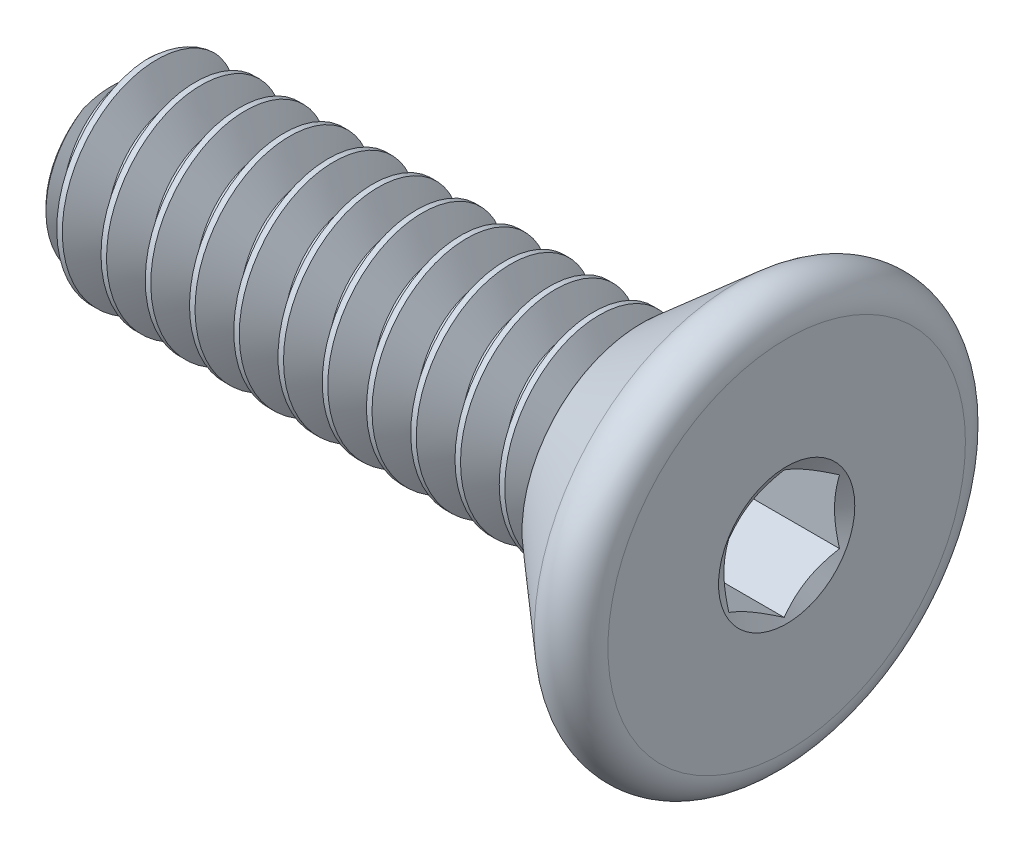
SolidWorks part; units mm, degrees
ref_plane "Front Plane" through (0, 0, 0) normal (0, 0, 1) x (1, 0, 0)
ref_plane "Top Plane" through (0, 0, 0) normal (0, 1, 0) x (1, 0, 0)
ref_plane "Right Plane" through (0, 0, 0) normal (1, 0, 0) x (0, 0, -1)
sketch "Sketch1" plane through (0, 0, 0) normal (0, 0, 1) x (1, 0, 0)
  line L0 (4.7625, 3.2385) -> (4.7625, -3.2385) construction
  line L1 (4.7625, 0) -> (-4.7625, 0) construction
  line L2 (-4.7625, 1.1049) -> (-4.7625, -1.1049) construction
  line L3 (-4.7625, 1.1049) -> (-4.445, 1.4224) construction
  line L4 (-4.445, 1.4224) -> (2.6543, 1.4224) construction
  line L8 (2.6543, 1.6941) -> (2.6543, -1.6941) construction
  line L9 (-4.7625, -1.1049) -> (-4.445, -1.4224) construction
  line L10 (-4.445, -1.4224) -> (2.6543, -1.4224) construction
  line L11 (2.6543, 1.6941) -> (4.037, 2.8961) construction
  line L12 (2.6543, -1.6941) -> (4.037, -2.8961) construction
  line L13 (4.3244, 2.7686) -> (4.3244, -2.7686) construction
  line L14 (2.6543, 1.6437) -> (2.7649, 1.6437) construction
  line L15 (2.7649, 1.6437) -> (2.7649, 1.533) construction
  line L16 (4.7625, 0.7937) -> (3.3655, 0.7937) construction
  line L17 (3.3655, 0.7937) -> (3.3655, -0.7938) construction
  line L18 (3.3655, -0.7938) -> (4.7625, -0.7938) construction
  line L19 (4.3244, -2.7686) -> (4.3244, -3.2385) construction
  line L20 (4.3244, 2.7686) -> (4.3244, 3.2385) construction
  arc A0 (4.037, 2.8961) -> (4.7625, 2.5655) centre (4.3244, 2.5655) cw construction
  arc A1 (4.037, -2.8961) -> (4.7625, -2.5655) centre (4.3244, -2.5655) ccw construction
  arc A2 (2.6543, 1.6437) -> (2.6924, 1.7272) centre (2.7649, 1.6437) cw construction
  arc A3 (2.6543, -1.6437) -> (2.6924, -1.7272) centre (2.7649, -1.6437) ccw construction
  arc A4 (2.5437, 1.4224) -> (2.6543, 1.533) centre (2.5437, 1.533) ccw construction
  point P10 (-4.1275, -1.4224)
  point P13 (2.6543, 0)
  point P18 (4.3244, 0)
  point P19 (4.3244, -3.0036)
  point P37 (3.3655, 0)
  point P38 (-3.4925, -1.4224)
  point P40 (4.3244, 3.0036)
  dimension "A Head Diameter Max" = 6.477
  dimension "D1" = 45
  dimension "Thread Diameter" = 2.8448
  dimension "D2" = 0.3175
  dimension "Thread Pitch" = 0.635
  dimension "H Head Height" = 2.1082
  dimension "Countersink Angle" = 82
  dimension "A Head Diameter Min" = 5.5372
  dimension "F Fillet Transition Dia" = 3.4544
  dimension "L Length" = 9.525
  dimension "J Drive Size" = 1.5875
  dimension "T Key Engagement" = 1.397
  dimension "D3" = 1.27
sketch "Sketch2" plane through (0, 0, 0) normal (1, 0, 0) x (0, 0, -1)
  line L0 (0, 3.2385) -> (0, -3.2385) construction
  line L1 (0, 0.9165) -> (-0.7937, 0.4583) construction
  line L2 (-0.7937, 0.4583) -> (-0.7937, -0.4583) construction
  line L3 (-0.7937, -0.4583) -> (0, -0.9165) construction
  line L4 (0, -0.9165) -> (0.7937, -0.4583) construction
  line L5 (0.7937, -0.4583) -> (0.7937, 0.4583) construction
  line L6 (0.7937, 0.4583) -> (0, 0.9165) construction
  circle A0 centre (0, 0) radius 3.0036 construction
  circle A1 centre (0, 0) radius 0.7937 construction
sketch "Sketch3" plane through (0, 0, 0) normal (0, 0, 1) x (1, 0, 0)
  line L0 (-4.445, 1.4224) -> (-4.7625, 1.1049)
  line L1 (-4.7625, 1.1049) -> (-4.7625, 0)
  line L2 (-4.7625, 0) -> (4.7625, 0)
  line L3 (4.7625, 0) -> (4.7625, 2.5655)
  line L5 (4.037, 2.8961) -> (2.6924, 1.7272)
  line L7 (2.6543, 1.6437) -> (2.6543, 1.533)
  line L9 (2.5437, 1.4224) -> (-4.445, 1.4224)
  arc A0 (4.037, 2.8961) -> (4.7625, 2.5655) centre (4.3244, 2.5655) cw
  arc A1 (2.6924, 1.7272) -> (2.6543, 1.6437) centre (2.7649, 1.6437) ccw
  arc A2 (2.6543, 1.533) -> (2.5437, 1.4224) centre (2.5437, 1.533) cw
revolve "Revolve1" add sketch "Sketch3" angle 360 about L1
sketch "Sketch4" plane through (4.7625, 0, 0) normal (1, 0, 0) x (0, 0, -1)
  line L1 (0, 0.9165) -> (-0.7937, 0.4583)
  line L2 (-0.7937, 0.4583) -> (-0.7937, -0.4583)
  line L3 (-0.7937, -0.4583) -> (0, -0.9165)
  line L4 (0, -0.9165) -> (0.7937, -0.4583)
  line L5 (0.7937, -0.4583) -> (0.7937, 0.4583)
  line L6 (0.7937, 0.4583) -> (0, 0.9165)
  circle A0 centre (0, 0) radius 0.7937 construction
extrude "Cut-Extrude1" cut sketch "Sketch4" against normal up to vertex (1.397 mm away) up to point (3.3655, 0.7937, 0)
sketch "Sketch5" plane through (4.7625, 0, 0) normal (1, 0, 0) x (0, 0, -1)
  line L0 (0, 0.9165) -> (0, 0.9779) construction
  line L1 (0, 0.9165) -> (0, 0.8551) construction
  line L2 (0, 0.8551) -> (0, 0.7937) construction
  circle A0 centre (0, 0) radius 0.9779
  circle A2 centre (0, 0) radius 0.7937 construction
extrude "Cut-Extrude2" cut sketch "Sketch5" against normal through all draft 60
sketch "Sketch6" plane through (3.3655, 0, 0) normal (1, 0, 0) x (0, 0, -1)
  circle A0 centre (0, 0) radius 0.7937
  circle A1 centre (0, 0) radius 0.7937 construction
extrude "Cut-Extrude3" cut sketch "Sketch6" against normal through all draft 60
split "Split1" bodies to split 107 resulting bodies 108 109 split by face at (2.6543, 0, -1.533)
sketch "Sketch7" plane through (0, 0, 0) normal (0, 0, 1) x (1, 0, 0)
  line L0 (-5.0403, -0.9412) -> (-5.3181, -1.4224) construction
  line L1 (-5.3181, -1.4224) -> (-4.7625, -1.4224) construction
  line L2 (-4.7625, -1.4224) -> (-5.0403, -0.9412) construction
  line L3 (-4.7625, -1.4224) -> (-4.7228, -1.4911) construction
  line L4 (-4.7228, -1.4911) -> (-5.3578, -1.4911) construction
  line L5 (-5.3578, -1.4911) -> (-5.3181, -1.4224) construction
  line L6 (-5.08, -1.01) -> (-5.0006, -1.01) construction
  line L7 (-5.0403, -1.4224) -> (-5.0403, -1.4911) construction
  line L8 (-5.0403, -0.9412) -> (-5.0403, -1.01) construction
  line L9 (-4.7625, 1.1049) -> (-4.7625, -1.1049) construction
  line L10 (-4.445, -1.4224) -> (2.6543, -1.4224) construction
  line L11 (-5.08, -1.01) -> (-5.338, -1.4568)
  line L12 (-5.338, -1.4568) -> (-4.7427, -1.4568)
  line L13 (-4.7427, -1.4568) -> (-5.0006, -1.01)
  line L14 (-5.0006, -1.01) -> (-5.08, -1.01)
  dimension "D1" = 0.635
  dimension "D2" = 0.0794
sketch "Sketch8" plane through (-4.7625, 0, 0) normal (-1, 0, 0) x (0, 0, 1)
  line L0 (0, 1.1049) -> (0, -1.1049) construction
  circle A0 centre (0, 0) radius 1.4224
curve "Helix/Spiral1" pitch 0.635 height 9.525 radius 1.4224 centre (-4.7625, 0, 0) axis (1, 0, 0) start towards (0, 0, 1)
sweep "Cut-Sweep1" cut profiles "Sketch7" path "Helix/Spiral1" align with end faces yes
combine bodies "Combine1" operation type add bodies to combine 110 109
equation "\"D2@Sketch1\"=\"Thread Pitch@Sketch1\"*.5"
equation "\"D1@Sketch7\"=\"Thread Pitch@Sketch1\""
equation "\"D2@Sketch7\"=\"D1@Sketch7\"/8"
equation "\"D4@Helix/Spiral1\"=\"Thread Pitch@Sketch1\""
equation "\"D3@Helix/Spiral1\"=\"L Length@Sketch1\""
equation "\"D3@Sketch1\"=\"Thread Pitch@Sketch1\"*2"
